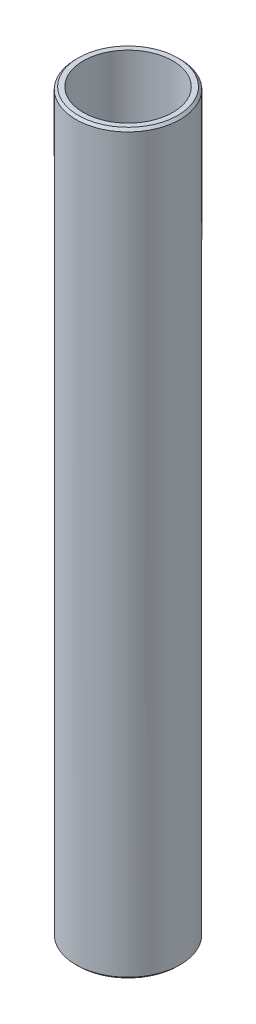
SolidWorks part; units mm, degrees
ref_plane "Front Plane" through (0, 0, 0) normal (0, 0, 1) x (1, 0, 0)
ref_plane "Top Plane" through (0, 0, 0) normal (0, 1, 0) x (1, 0, 0)
ref_plane "Right Plane" through (0, 0, 0) normal (1, 0, 0) x (0, 0, -1)
sketch "Sketch1" plane through (0, 0, 0) normal (0, 1, 0) x (1, 0, 0)
  circle A0 centre (0, 0) radius 42.5
  dimension "SHAFT_OD" = 85
extrude "Boss-Extrude1" add sketch "Sketch1" along normal blind 600
sketch "Sketch2" plane through (0, 0, 0) normal (0, 1, 0) x (1, 0, 0)
  circle A0 centre (0, 0) radius 36.4489
  dimension "BORE_D" = 72.8978
extrude "Cut-Extrude1" cut sketch "Sketch2" along normal through all
chamfer "Chamfer1" distance 1.9305 angle 45 2 edges at (0, 600, 42.5) (0, 0, 42.5)
